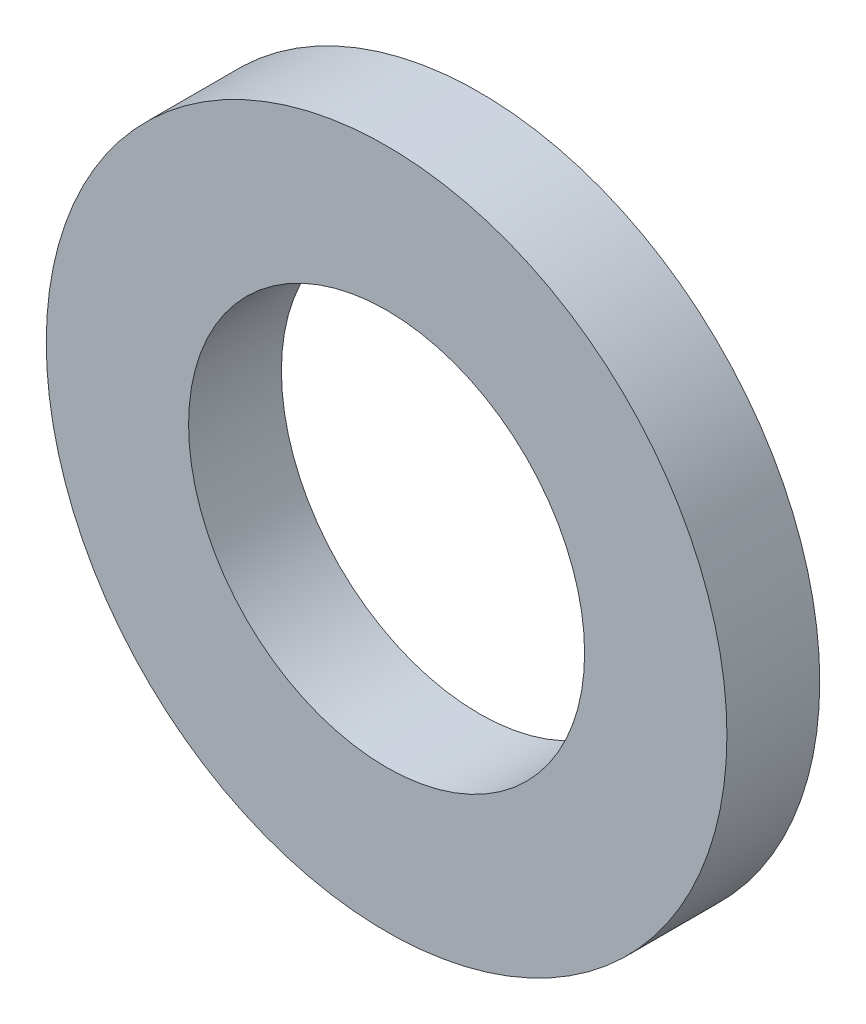
SolidWorks part; units mm, degrees
ref_plane "Front Plane" through (0, 0, 0) normal (0, 0, 1) x (1, 0, 0)
ref_plane "Top Plane" through (0, 0, 0) normal (0, 1, 0) x (1, 0, 0)
ref_plane "Right Plane" through (0, 0, 0) normal (1, 0, 0) x (0, 0, -1)
sketch "Sketch1" plane through (0, 0, 0) normal (0, 0, 1) x (1, 0, 0)
  circle A0 centre (0, 0) radius 5.5
  circle A1 centre (0, 0) radius 3.2
  dimension "OD" = 11
  dimension "ID1" = 6.4
extrude "Boss-Extrude1" add sketch "Sketch1" along normal blind 1.5
ref_axis "Center Axis 1" through (0, 0, 1.5) along (0, 0, -1)
ref_plane "Contact Plane 1" through (0, 0, 1.5) normal (0, 0, 1) x (1, 0, 0)
ref_plane "Contact Plane 2" through (0, 0, 0) normal (0, 0, -1) x (-1, 0, 0)
